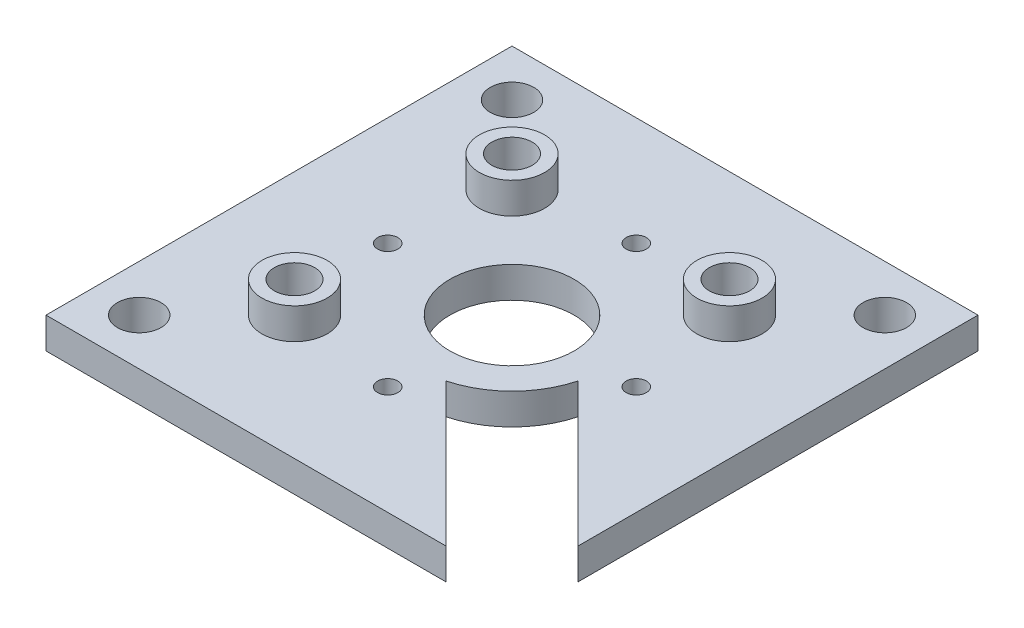
SolidWorks part; units mm, degrees
ref_plane "前视基准面" through (0, 0, 0) normal (0, 0, 1) x (1, 0, 0)
ref_plane "上视基准面" through (0, 0, 0) normal (0, 1, 0) x (1, 0, 0)
ref_plane "右视基准面" through (0, 0, 0) normal (1, 0, 0) x (0, 0, -1)
sketch "草图1" plane through (0, 0, 0) normal (0, 1, 0) x (1, 0, 0)
  line L0 (0, 0) -> (8, 0) construction
  line L1 (0, 0) -> (0, 8) construction
  line L3 (-15, 15) -> (15, 15)
  line L4 (-15, 15) -> (-15, -15)
  line L5 (-15, -15) -> (15, -15)
  line L6 (15, 15) -> (15, -15)
  circle A0 centre (0, 0) radius 8 construction
  circle A1 centre (8, 0) radius 0.65
  circle A2 centre (0, -8) radius 0.65
  circle A3 centre (-8, 0) radius 0.65
  circle A4 centre (0, 8) radius 0.65
  circle A5 centre (0, 0) radius 4
  circle A6 centre (0, 0) radius 15 construction
  circle A7 centre (12, 12) radius 1.4
  circle A8 centre (-12, 12) radius 1.4
  circle A9 centre (12, -12) radius 1.4
  circle A10 centre (-12, -12) radius 1.4
  point P28 (14.2863, -4.4696)
  dimension "D1" = 16
  dimension "D2" = 1.3
  dimension "D4" = 8
  dimension "D5" = 30
  dimension "D6" = 2.8
  dimension "D7" = 24
  dimension "D8" = 24
  dimension "D3" = 4
extrude "凸台-拉伸1" add sketch "草图1" along normal blind 2 contours L6 L3 L4 L5 A10 A8 A7 A5 A4 A3 A2 A1 A9 region at (0, 0, -14.5757)
sketch "草图2" plane through (0, 2, 0) normal (0, 1, 0) x (1, 0, 0)
  line L0 (0, 0) -> (7, 7) construction
  line L1 (0, 0) -> (9.8995, 0) construction
  line L2 (5.7956, -1.5529) -> (15, -10.7574)
  line L3 (15, 15) -> (15, -15) construction
  line L4 (0, 0) -> (15, -15) construction
  line L5 (1.5529, -5.7956) -> (10.7574, -15)
  line L6 (15, -10.7574) -> (15, -15)
  line L7 (15, -15) -> (10.7574, -15)
  circle A0 centre (0, 0) radius 9.8995 construction
  circle A1 centre (7, 7) radius 1.3
  circle A2 centre (7, 7) radius 2.1
  circle A3 centre (7, -7) radius 2.1
  circle A4 centre (7, -7) radius 1.3
  circle A5 centre (-7, -7) radius 2.1
  circle A6 centre (-7, -7) radius 1.3
  circle A7 centre (-7, 7) radius 2.1
  circle A8 centre (-7, 7) radius 1.3
  circle A9 centre (0, 0) radius 6 construction
  arc A10 (5.7956, -1.5529) -> (1.5529, -5.7956) centre (0, 0) cw
  line M20 (15, -15) -> (15, 15)
  line M23 (-15, -15) -> (15, -15)
  circle M24 centre (12, -12) radius 1.4
  dimension "D1" = 2.6
  dimension "D2" = 4.2
  dimension "D6" = 12
  dimension "D4" = 45
  dimension "D5" = 14
  dimension "D7" = 6
  dimension "D3" = 4
extrude "凸台-拉伸3" add sketch "草图2" along normal blind 2 contours A5 A6 | A7 A8 | A2 A1 region at (4.9594, 2, -7) region at (-9.0406, 2, 7) region at (-9.0406, 2, -7)
extrude "切除-拉伸2" cut sketch "草图2<6>" against normal up to surface (2 mm away) contours A8 | A6 | A1 | A3 A4 | A4 | L2 A10 L5 A3 M23 M20 M24 region at (9.1664, 2, 9.1664) region at (7, 2, -7) region at (4.9594, 2, 7) region at (7, 2, 7) region at (-7, 2, 7) region at (-7, 2, -7) up to face at (-12, 0, 13.4)
sketch "草图2<6>" plane through (0, 2, 0) normal (0, 1, 0) x (1, 0, 0) same geometry as "草图2"
